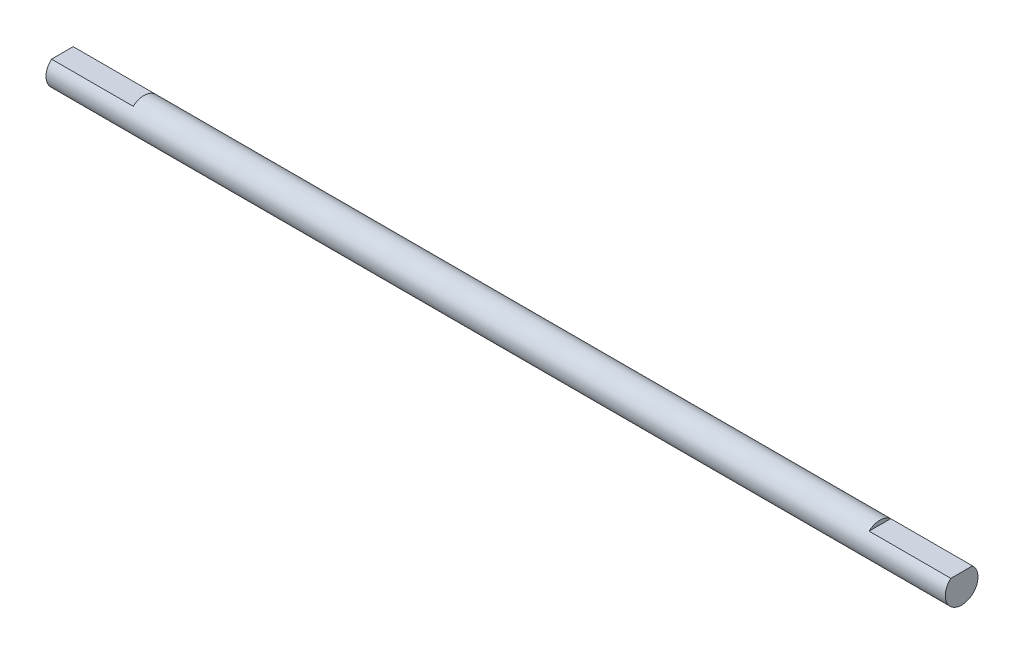
SolidWorks part; units mm, degrees
ref_plane "Front Plane" through (0, 0, 0) normal (0, 0, 1) x (1, 0, 0)
ref_plane "Top Plane" through (0, 0, 0) normal (0, 1, 0) x (1, 0, 0)
ref_plane "Right Plane" through (0, 0, 0) normal (1, 0, 0) x (0, 0, -1)
sketch "Sketch1" plane through (0, 0, 0) normal (1, 0, 0) x (0, 0, -1)
  line L0 (-1.3229, 1.5) -> (1.3229, 1.5)
  arc A0 (-1.3229, 1.5) -> (1.3229, 1.5) centre (0, 0) ccw
  dimension "D1" = 4
  dimension "D2" = 1.5
extrude "Boss-Extrude1" add sketch "Sketch1" along normal mid plane 110
sketch "Sketch2" plane through (0, 0, 0) normal (1, 0, 0) x (0, 0, -1)
  circle A0 centre (0, 0) radius 2
  arc A1 (-1.3229, 1.5) -> (1.3229, 1.5) centre (0, 0) ccw construction
extrude "Boss-Extrude2" add sketch "Sketch2" along normal mid plane 90
